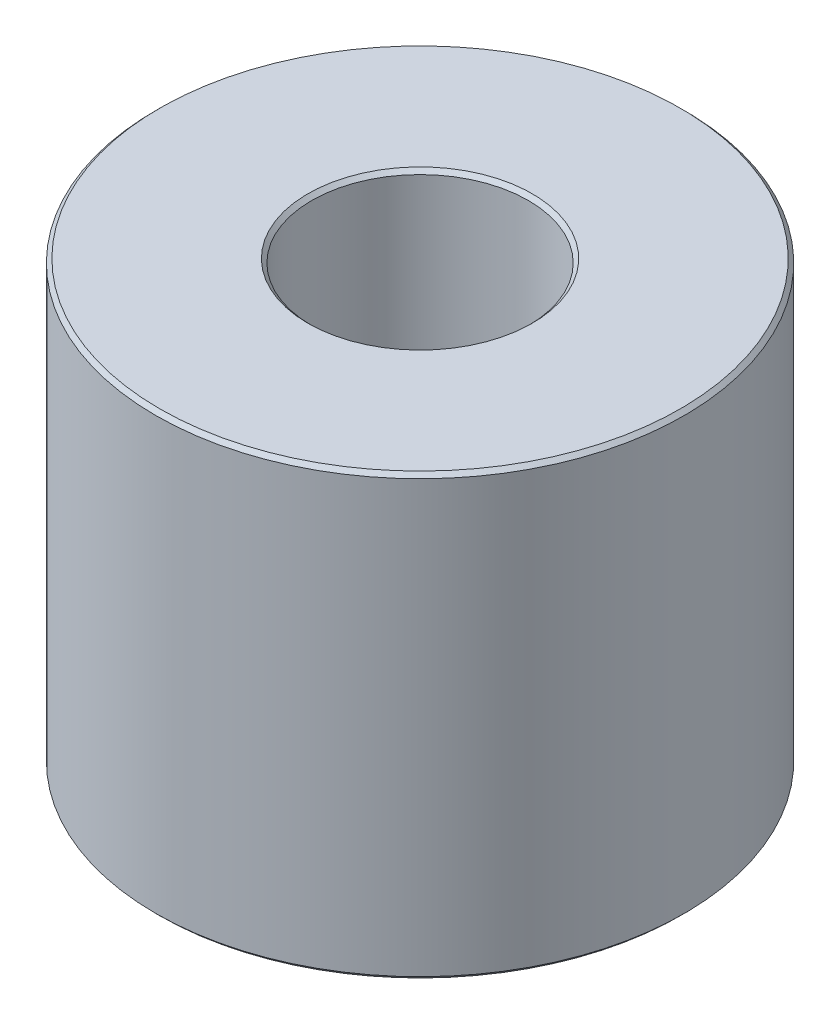
SolidWorks part; units mm, degrees
ref_plane "Front Plane" through (0, 0, 0) normal (0, 0, 1) x (1, 0, 0)
ref_plane "Top Plane" through (0, 0, 0) normal (0, 1, 0) x (1, 0, 0)
ref_plane "Right Plane" through (0, 0, 0) normal (1, 0, 0) x (0, 0, -1)
sketch "Sketch1" plane through (0, 0, 0) normal (0, 1, 0) x (1, 0, 0)
  circle A0 centre (0, 0) radius 17.5
  dimension "SLEEVE_OD" = 35
extrude "Boss-Extrude1" add sketch "Sketch1" along normal blind 29.0743
sketch "Sketch2" plane through (0, 0, 0) normal (0, 1, 0) x (1, 0, 0)
  circle A0 centre (0, 0) radius 7.1736
  dimension "BORE_D" = 14.3472
extrude "Cut-Extrude1" cut sketch "Sketch2" along normal through all
chamfer "Chamfer1" distance 0.2575 angle 45 4 edges at (0, 29.0743, 7.1736) (0, 0, 7.1736) (0, 0, 17.5) (0, 29.0743, 17.5)
